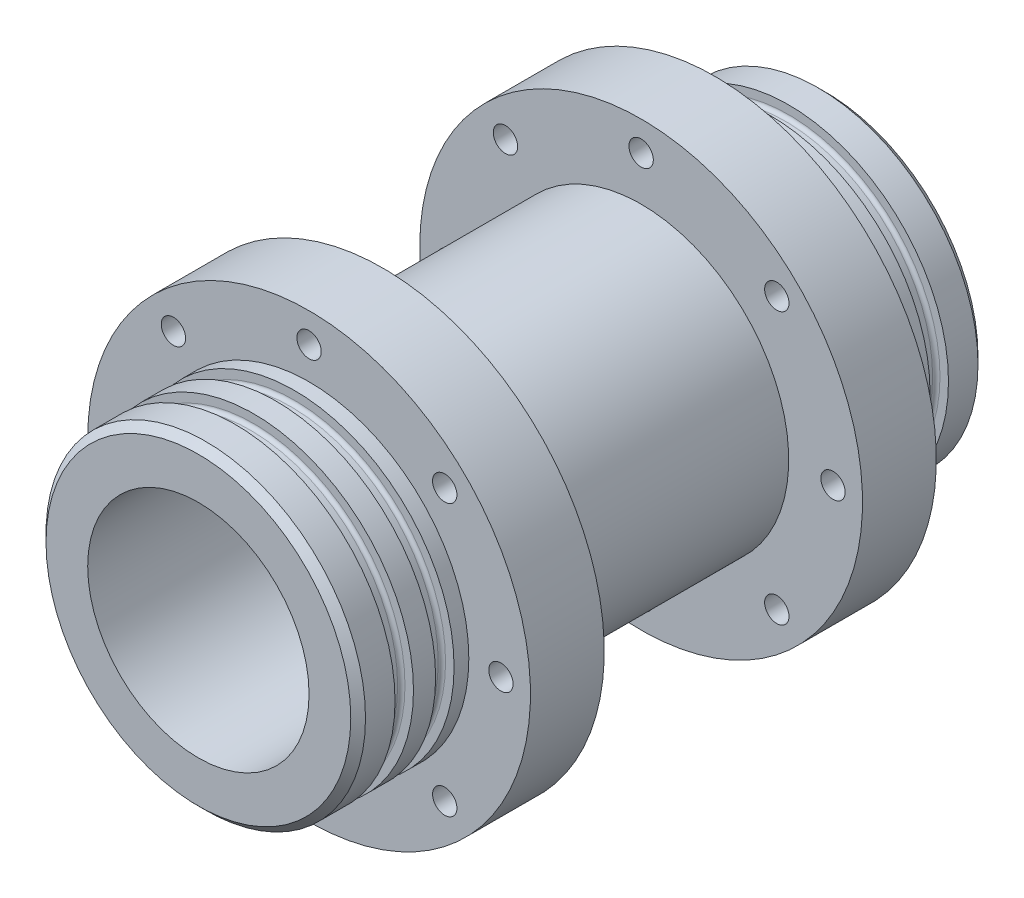
SolidWorks part; units mm, degrees
ref_plane "Front Plane" through (0, 0, 0) normal (0, 0, 1) x (1, 0, 0)
ref_plane "Top Plane" through (0, 0, 0) normal (0, 1, 0) x (1, 0, 0)
ref_plane "Right Plane" through (0, 0, 0) normal (1, 0, 0) x (0, 0, -1)
sketch "Sketch1" plane through (0, 0, 0) normal (0, 0, 1) x (1, 0, 0)
  circle A0 centre (0, 0) radius 15
  circle A1 centre (0, 0) radius 20
  dimension "D1" = 30
  dimension "D2" = 40
extrude "Boss-Extrude1" add sketch "Sketch1" along normal mid plane 85
ref_plane "Plane1" through (0, 0, -27.5) normal (0, 0, -1) x (-1, 0, 0)
sketch "Sketch2" plane through (0, 0, -27.5) normal (0, 0, -1) x (-1, 0, 0)
  circle A0 centre (0, 0) radius 30
  circle A1 centre (0, 0) radius 20 construction
  circle A2 centre (0, 0) radius 20
  dimension "D1" = 60
extrude "Boss-Extrude2" add sketch "Sketch2" against normal blind 10
sketch "Sketch3" plane through (0, 0, -27.5) normal (0, 0, -1) x (-1, 0, 0)
  circle A0 centre (0, 0) radius 21.65
  circle A1 centre (0, 0) radius 20 construction
  circle A2 centre (0, 0) radius 20
  dimension "D1" = 1.65
extrude "Boss-Extrude3" add sketch "Sketch3" along normal blind 15
sketch "Sketch4" plane through (0, 0, 0) normal (1, 0, 0) x (0, 0, -1)
  line L0 (29.5, 21.65) -> (29.5, 20)
  line L1 (42.5, 21.65) -> (27.5, 21.65) construction
  line L2 (29.5, 20) -> (32, 20)
  line L3 (32, 20) -> (32, 21.65)
  line L4 (32, 21.65) -> (29.5, 21.65)
  line L5 (35, 21.65) -> (35, 20)
  line L6 (35, 20) -> (37.5, 20)
  line L7 (37.5, 20) -> (37.5, 21.65)
  line L8 (37.5, 21.65) -> (35, 21.65)
  line L9 (27.5, -23.1799) -> (27.5, 23.1799) construction
  line L10 (0, 0) -> (48.8823, 0) construction
  dimension "D1" = 2.5
  dimension "D2" = 2
  dimension "D3" = 1.65
  dimension "D4" = 3
revolve "Cut-Revolve1" cut sketch "Sketch4" angle 360 about L10
chamfer "Chamfer1" distance 1 angle 45 1 edges at (-21.65, 0, -42.5)
hole_wizard "M4 Tapped Hole1" positions "Sketch5" profile "Sketch6" tap size "M4" standard "ISO" end condition up to next
sketch "Sketch5" plane through (0, 0, -27.5) normal (0, 0, -1) x (-1, 0, 0)
  point P0 (0, 26)
  dimension "D1" = 26
sketch "Sketch6" plane through (0, 26, -27.5) normal (1, 0, 0) x (0, 1, 0)
  line L0 (0, 0) -> (0, 10)
  line L1 (0, 10) -> (1.65, 10)
  line L2 (1.65, 10) -> (1.65, 0)
  line L5 (1.65, 0) -> (0, 0)
  line L11 (0, -6.35) -> (0, 107.95) construction
  dimension "Thru Tap Drill Dia." = 3.3
  dimension "Thru Tap Drill Depth" = 10
cosmetic thread "Hole Thread1" parameters "D2"=4
pattern_circular "CirPattern1" count 8 over 360 about axis through (0, 0, -27.5) along (0, 0, -1) of "M4 Tapped Hole1"
cosmetic thread "Hole Thread2"
cosmetic thread "Hole Thread3"
cosmetic thread "Hole Thread4"
cosmetic thread "Hole Thread5"
cosmetic thread "Hole Thread6"
cosmetic thread "Hole Thread7"
cosmetic thread "Hole Thread8"
fillet "Fillet1" radius 0.5 4 edges at (20, 0, -35) (20, 0, -37.5) (20, 0, -32) (20, 0, -29.5)
mirror "Mirror2" about plane through (0, 0, 0) normal (0, 0, 1) of "Fillet1", "Boss-Extrude2", "Boss-Extrude3", "Cut-Revolve1", "Chamfer1", "M4 Tapped Hole1", "CirPattern1"
cosmetic thread "Hole Thread17"
cosmetic thread "Hole Thread18"
cosmetic thread "Hole Thread19"
cosmetic thread "Hole Thread20"
cosmetic thread "Hole Thread21"
cosmetic thread "Hole Thread22"
cosmetic thread "Hole Thread23"
cosmetic thread "Hole Thread24"
